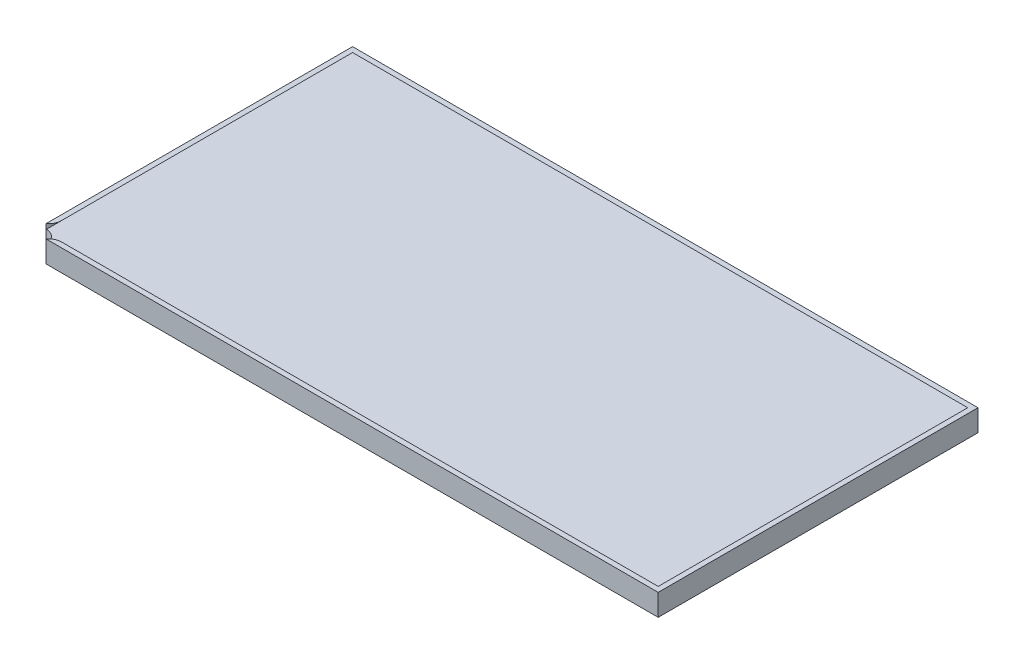
SolidWorks part; units mm, degrees
ref_plane "Płaszczyzna przednia" through (0, 0, 0) normal (0, 0, 1) x (1, 0, 0)
ref_plane "Płaszczyzna górna" through (0, 0, 0) normal (0, 1, 0) x (1, 0, 0)
ref_plane "Płaszczyzna prawa" through (0, 0, 0) normal (1, 0, 0) x (0, 0, -1)
sketch "Szkic4" plane through (0, 0, 0) normal (0, 1, 0) x (1, 0, 0)
  line L1 (-1784.5, -889) -> (1784.5, -889)
  line L2 (-1784.5, -889) -> (-1784.5, 889)
  line L3 (-1784.5, 889) -> (1784.5, 889)
  line L4 (1784.5, -889) -> (1784.5, 889)
  line L5 (-1784.5, -889) -> (1784.5, 889) construction
  line L6 (-1784.5, 889) -> (1784.5, -889) construction
  line L7 (-1832.5, -937) -> (1832.5, -937)
  line L8 (-1832.5, -937) -> (-1832.5, 937)
  line L9 (-1832.5, 937) -> (1832.5, 937)
  line L10 (1832.5, -937) -> (1832.5, 937)
  line L11 (-1832.5, -937) -> (1832.5, 937) construction
  line L12 (-1832.5, 937) -> (1832.5, -937) construction
  point P0 (0, 0)
  point P6 (0, 0)
  dimension "D1" = 3569
  dimension "D2" = 1778
  dimension "D3" = 48
  dimension "D4" = 48
extrude "Dodanie-wyciągnięcie3" add sketch "Szkic4" along normal blind 27
chamfer "Sfazowanie1" distance 45 angle 45 4 edges at (0, 0, 889) (-1784.5, 0, 0) (0, 0, -889) (1784.5, 0, 0)
sketch "Szkic5" plane through (0, 0, 0) normal (0, -1, 0) x (1, 0, 0)
  line L1 (-1832.5, -937) -> (1832.5, -937)
  line L2 (-1832.5, -937) -> (-1832.5, 937)
  line L3 (-1832.5, 937) -> (1832.5, 937)
  line L4 (1832.5, -937) -> (1832.5, 937)
  line L5 (-1832.5, -937) -> (1832.5, 937) construction
  line L6 (-1832.5, 937) -> (1832.5, -937) construction
  point P0 (0, 0)
extrude "Dodanie-wyciągnięcie4" add sketch "Szkic5" along normal blind 100
sketch "Szkic6" plane through (0, 27, 0) normal (0, 1, 0) x (1, 0, 0)
  line L0 (-1832.5, -937) -> (-1832.5, -799)
  line L1 (-1832.5, 937) -> (-1832.5, -937) construction
  line L2 (-1832.5, -937) -> (-1694.5, -937)
  line L3 (-1832.5, -937) -> (1832.5, -937) construction
  line L4 (-1694.5, -907) -> (-1694.5, -983.2)
  line L5 (1802.5, -907) -> (-1802.5, -907) construction
  line L6 (-1802.5, -799) -> (-1878.7, -799)
  line L7 (-1802.5, -907) -> (-1802.5, 907) construction
  line L8 (-1832.5, -799) -> (-1832.5, -937)
  line L9 (-1802.5, -799) -> (-1802.5, -907)
  line L10 (-1802.5, -907) -> (-1694.5, -907)
  circle A0 centre (-1694.5, -983.2) radius 76.2
  circle A1 centre (-1878.7, -799) radius 76.2
  line M2 (1802.5, -907) -> (-1802.5, -907)
  line M3 (-1802.5, -907) -> (-1802.5, 907)
  line M8 (-1832.5, -937) -> (1832.5, -937)
  dimension "D4" = 152.4
  dimension "D6" = 152.4
  dimension "D1" = 138
  dimension "D2" = 138
  dimension "D3" = 76.2
  dimension "D5" = 76.2
extrude "Wytnij-wyciągnięcie1" cut sketch "Szkic6" against normal up to surface (27 mm away) contours A1 L8 A0 M8 M2 M3 region at (-1830.5484, 27, 898.2985) up to face at (0, 0, 0)
sketch "Szkic7" plane through (0, 0, 0) normal (0, 1, 0) x (1, 0, 0)
  circle A0 centre (-1832.5, -937) radius 77.403
extrude "Wytnij-wyciągnięcie2" cut sketch "Szkic7" against normal up to next
